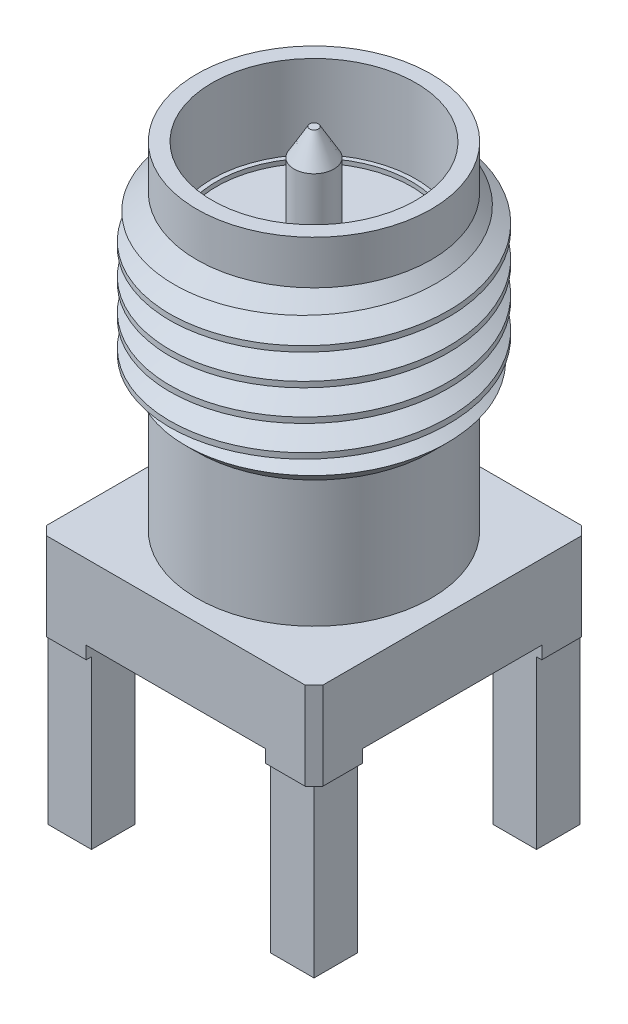
SolidWorks part; units mm, degrees
material "Aluminum Bronze"
ref_plane "Спереди" through (0, 0, 0) normal (0, 0, 1) x (1, 0, 0)
ref_plane "Сверху" through (0, 0, 0) normal (0, 1, 0) x (1, 0, 0)
ref_plane "Справа" through (0, 0, 0) normal (1, 0, 0) x (0, 0, -1)
sketch "Эскиз1" plane through (0, 0, 0) normal (0, 0, 1) x (1, 0, 0)
  line L2 (-2.675, 5.81) -> (-2.675, 8.7)
  line L3 (-2.675, 8.7) -> (-3.175, 9.2)
  line L4 (-3.175, 9.2) -> (-3.175, 12)
  line L5 (-3.175, 12) -> (-2.675, 12.5)
  line L6 (-2.675, 12.5) -> (-2.675, 13.5)
  line L7 (-2.675, 13.5) -> (-2.325, 13.5)
  line L8 (-2.325, 13.5) -> (-2.325, 11.6)
  line L9 (-2.325, 11.6) -> (-2.225, 11.6)
  line L10 (-2.225, 11.6) -> (-2.225, 11.5)
  line L11 (-2.225, 11.5) -> (-0.455, 11.5)
  line L12 (-0.455, 11.5) -> (-0.455, 13.1851)
  line L13 (-0.455, 13.1851) -> (-0.1, 13.8)
  line L14 (-0.1, 13.8) -> (0, 13.8)
  line L15 (-2.675, 5.81) -> (-0.635, 5.81)
  line L16 (0, 6.9) -> (0, 13.8)
  line L18 (0, 0) -> (0, 6.9)
  line L19 (0, 0) -> (-0.635, 0)
  line L20 (-0.635, 0) -> (-0.635, 5.81)
  line L21 (0, -1000) -> (0, 49000) construction
  dimension "D2" = 6.35
  dimension "D3" = 2.89
  dimension "D4" = 45
  dimension "D5" = 13.5
  dimension "D6" = 1
  dimension "D7" = 4.65
  dimension "D8" = 2
  dimension "D9" = 0.455
  dimension "D10" = 1.9
  dimension "D11" = 0.1
  dimension "D12" = 0.3
  dimension "D13" = 30
  dimension "D14" = 0.2
  dimension "D15" = 5.35
  dimension "D16" = 1.27
revolve "Повернуть1" add sketch "Эскиз1" angle 360 about L21
sketch "Эскиз2" plane through (0, 5.81, 0) normal (0, -1, 0) x (1, 0, 0)
  line L0 (2.955, -3.155) -> (3.155, -2.955)
  line L1 (-2.955, -3.155) -> (2.955, -3.155)
  line L2 (-3.155, -2.955) -> (-3.155, 2.955)
  line L3 (-2.955, 3.155) -> (2.955, 3.155)
  line L4 (3.155, -2.955) -> (3.155, 2.955)
  line L5 (-3.155, -3.155) -> (3.155, 3.155) construction
  line L6 (-3.155, 3.155) -> (3.155, -3.155) construction
  line L7 (3.155, 2.955) -> (2.955, 3.155)
  line L8 (-3.155, 2.955) -> (-2.955, 3.155)
  line L9 (-2.955, -3.155) -> (-3.155, -2.955)
  point P0 (0, 0)
  dimension "D1" = 6.31
extrude "Бобышка-Вытянуть1" add sketch "Эскиз2" along normal blind 2
sketch "Эскиз3" plane through (0, 3.81, 0) normal (0, -1, 0) x (1, 0, 0)
  line L1 (2.54, -2.54) -> (-2.54, -2.54) construction
  line L2 (2.54, -2.54) -> (2.54, 2.54) construction
  line L3 (2.54, 2.54) -> (-2.54, 2.54) construction
  line L4 (-2.54, -2.54) -> (-2.54, 2.54) construction
  line L5 (2.54, -2.54) -> (-2.54, 2.54) construction
  line L6 (2.54, 2.54) -> (-2.54, -2.54) construction
  line L7 (-2.045, 3.035) -> (-3.035, 3.035)
  line L8 (-2.045, 3.035) -> (-2.045, 2.045)
  line L9 (-2.045, 2.045) -> (-3.035, 2.045)
  line L10 (-3.035, 3.035) -> (-3.035, 2.045)
  line L11 (-2.045, 3.035) -> (-3.035, 2.045) construction
  line L12 (-2.045, 2.045) -> (-3.035, 3.035) construction
  line L13 (-2.045, -2.045) -> (-3.035, -2.045)
  line L14 (-2.045, -2.045) -> (-2.045, -3.035)
  line L15 (-2.045, -3.035) -> (-3.035, -3.035)
  line L16 (-3.035, -2.045) -> (-3.035, -3.035)
  line L17 (-2.045, -2.045) -> (-3.035, -3.035) construction
  line L18 (-2.045, -3.035) -> (-3.035, -2.045) construction
  line L19 (3.035, -2.045) -> (2.045, -2.045)
  line L20 (3.035, -2.045) -> (3.035, -3.035)
  line L21 (3.035, -3.035) -> (2.045, -3.035)
  line L22 (2.045, -2.045) -> (2.045, -3.035)
  line L23 (3.035, -2.045) -> (2.045, -3.035) construction
  line L24 (3.035, -3.035) -> (2.045, -2.045) construction
  line L25 (3.035, 2.045) -> (2.045, 2.045)
  line L26 (3.035, 2.045) -> (3.035, 3.035)
  line L27 (3.035, 3.035) -> (2.045, 3.035)
  line L28 (2.045, 2.045) -> (2.045, 3.035)
  line L29 (3.035, 2.045) -> (2.045, 3.035) construction
  line L30 (3.035, 3.035) -> (2.045, 2.045) construction
  circle A0 centre (-2.54, 2.54) radius 0.7 construction
  point P0 (0, 0)
  dimension "D3" = 1.4
  dimension "D2" = 5.08
extrude "Бобышка-Вытянуть2" add sketch "Эскиз3" along normal blind 3.81
sketch "Эскиз8" plane through (0, 3.81, 0) normal (0, -1, 0) x (1, 0, 0)
  line L0 (-1002.4819, 2.045) -> (48997.5181, 2.045) construction
  line L2 (-1002.54, -2.045) -> (48997.46, -2.045) construction
  line L3 (-2.045, -2.045) -> (-3.035, -2.045) construction
  line L4 (-2.045, -997.5444) -> (-2.045, 49002.4556) construction
  line L6 (2.045, -997.693) -> (2.045, 49002.307) construction
  line L8 (-3.155, 2.955) -> (-3.155, -2.955) construction
  line L9 (3.155, -2.955) -> (3.155, 2.955) construction
  line L10 (-2.955, -3.155) -> (2.955, -3.155) construction
  line L11 (2.955, 3.155) -> (-2.955, 3.155) construction
  line L12 (-2.045, -2.045) -> (-2.045, -3.155)
  line L13 (-2.045, 3.155) -> (2.045, 3.155)
  line L14 (-2.045, 3.155) -> (-2.045, 2.045)
  line L15 (-2.045, -3.155) -> (2.045, -3.155)
  line L16 (2.045, 3.155) -> (2.045, 2.045)
  line L17 (3.155, 2.045) -> (2.045, 2.045)
  line L18 (3.155, 2.045) -> (3.155, -2.045)
  line L19 (3.155, -2.045) -> (2.045, -2.045)
  line L20 (-3.155, 2.045) -> (-3.155, -2.045)
  line L21 (-2.045, 2.045) -> (-3.155, 2.045)
  line L22 (2.045, -2.045) -> (2.045, -3.155)
  line L23 (-2.045, -2.045) -> (-3.155, -2.045)
  circle A0 centre (0, 0) radius 0.635
  point P7 (-2.54, -2.045)
  point P10 (-3.155, 2.045)
  point P12 (-3.155, -2.045)
  point P15 (3.155, -2.045)
  point P16 (2.045, -3.155)
  point P19 (-2.045, -3.155)
  point P22 (-2.045, 3.155)
  point P23 (2.045, 3.155)
extrude "Вырез-Вытянуть2" cut sketch "Эскиз8" against normal offset from surface (0.29 mm away) 9.4
sketch "Эскиз4" plane through (0, 4.1, 0) normal (0, -1, 0) x (1, 0, 0)
  circle A0 centre (0, 0) radius 0.635
  circle A1 centre (0, 0) radius 2.5
  point P5 (0, 0)
  dimension "D1" = 5
extrude "Вырез-Вытянуть1" cut sketch "Эскиз4" against normal blind 0.1
sketch "Эскиз5" plane through (0, 13.5, 0) normal (0, 1, 0) x (1, 0, 0)
  circle A0 centre (0, 0) radius 2.675
curve "Спираль1" pitch 0.705 height 4.935 turns 7
sketch "Эскиз6" plane through (0, 0, 0) normal (0, 0, 1) x (1, 0, 0)
  line L0 (2.675, 13.5) -> (3.675, 12.9226)
  line L1 (3.675, 12.9226) -> (3.675, 14.0774)
  line L2 (3.675, 14.0774) -> (2.675, 13.5)
  line L3 (2.675, 13.5) -> (3.675, 13.5) construction
  point P6 (3.675, 13.5)
  dimension "D1" = 60
  dimension "D2" = 1
sweep "Вырез-По траектории1" cut profiles "Эскиз6" path "Спираль1"
